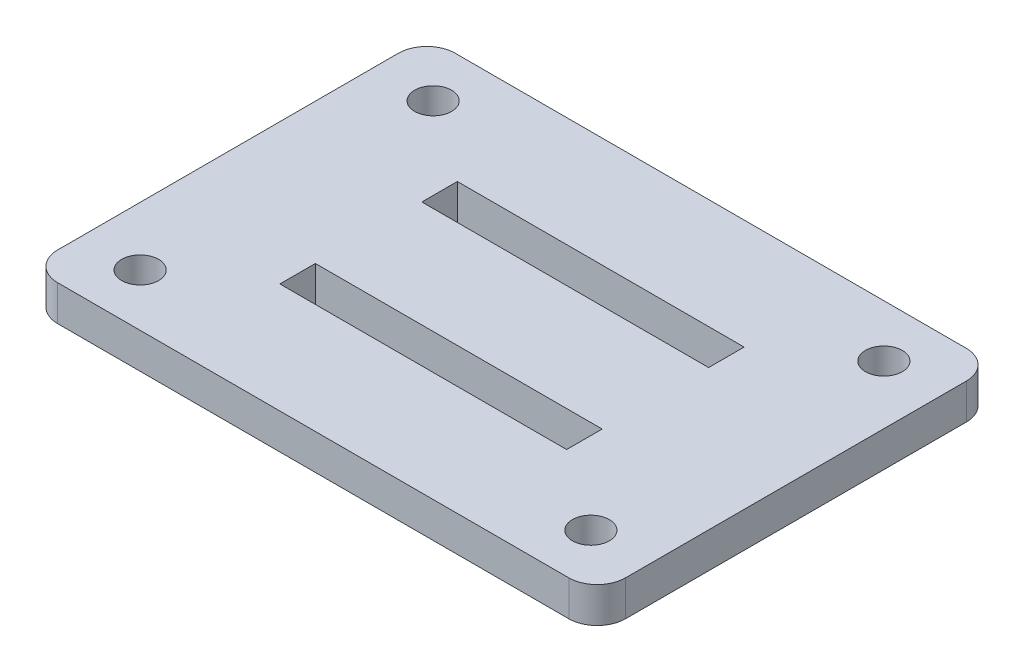
SolidWorks part; units mm, degrees
other "标注1"
sketch "草图8" plane through (-40, 4.6, -28) normal (0, 1, 0) x (1, 0, 0)
ref_plane "前视基准面" through (0, 0, 0) normal (0, 0, 1) x (1, 0, 0)
ref_plane "上视基准面" through (0, 0, 0) normal (0, 1, 0) x (1, 0, 0)
ref_plane "右视基准面" through (0, 0, 0) normal (1, 0, 0) x (0, 0, -1)
other "Configuration Table"
sketch "草图1" plane through (0, 0, 0) normal (0, 1, 0) x (1, 0, 0)
  line L0 (-89.3251, 0) -> (102.0425, 0) construction
  line L1 (0, 56.7239) -> (0, -62.578) construction
  line L2 (-20.2, -7.5) -> (20.2, -7.5)
  line L3 (-20.2, 12.5) -> (20.2, 12.5)
  line L4 (-20.2, 12.5) -> (-20.2, 7.5)
  line L5 (-20.2, 7.5) -> (20.2, 7.5)
  line L6 (20.2, 12.5) -> (20.2, 7.5)
  line L7 (-20.2, 12.5) -> (20.2, 7.5) construction
  line L8 (-20.2, 7.5) -> (20.2, 12.5) construction
  line L9 (20.2, -12.5) -> (20.2, -7.5)
  line L10 (-20.2, -12.5) -> (20.2, -12.5)
  line L11 (-20.2, -12.5) -> (-20.2, -7.5)
  circle A0 centre (-31.75, 20.6375) radius 2.6
  circle A4 centre (31.75, 20.6375) radius 2.6
  circle A5 centre (31.75, -20.6375) radius 2.6
  circle A6 centre (-31.75, -20.6375) radius 2.6
  point P13 (0, 10)
  dimension "D5" = 5.2
  dimension "D9" = 5.2
  dimension "D7" = 10
  dimension "D1" = 40.4
  dimension "D2" = 31.75
  dimension "D3" = 5
  dimension "D4" = 20.6375
  dimension "D8" = 5
  dimension "D10" = 40.4
  dimension "D11" = 8.1375
  dimension "D12" = 31.75
sketch "草图3" plane through (0, 0, 0) normal (0, 1, 0) x (1, 0, 0)
  line L1 (-40, -28) -> (40, -28)
  line L2 (-40, -28) -> (-40, 28)
  line L3 (-40, 28) -> (40, 28)
  line L4 (40, -28) -> (40, 28)
  line L5 (-40, -28) -> (40, 28) construction
  line L6 (-40, 28) -> (40, -28) construction
  point P0 (0, 0)
  dimension "D1" = 56
  dimension "D2" = 80
extrude "凸台-拉伸1" add sketch "草图3" along normal blind 5
extrude "切除-拉伸1" cut sketch "草图1" along normal up to surface (5 mm away) up to face at (0, 5, 0)
fillet "圆角2" radius 4 4 edges at (-40, 2.5, -28) (40, 2.5, -28) (40, 2.5, 28) (-40, 2.5, 28)
